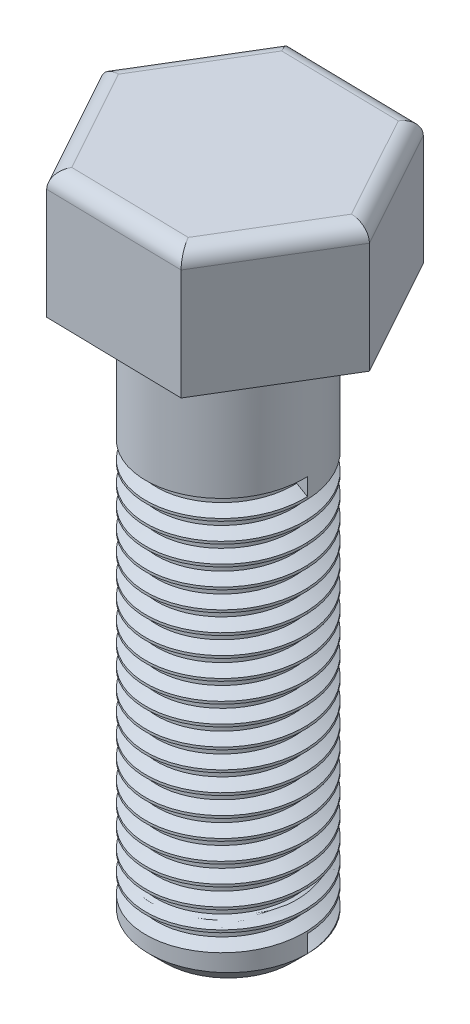
SolidWorks part; units mm, degrees
ref_plane "Front Plane" through (0, 0, 0) normal (0, 0, 1) x (1, 0, 0)
ref_plane "Top Plane" through (0, 0, 0) normal (0, 1, 0) x (1, 0, 0)
ref_plane "Right Plane" through (0, 0, 0) normal (1, 0, 0) x (0, 0, -1)
sketch "Sketch1" plane through (0, 0, 0) normal (0, 1, 0) x (1, 0, 0)
  circle A0 centre (0, 0) radius 5
  dimension "D1" = 10
extrude "Boss-Extrude1" add sketch "Sketch1" along normal blind 35
sketch "Sketch4" plane through (0, 35, 0) normal (0, 1, 0) x (1, 0, 0)
  line L1 (4.9182, 7.3997) -> (-3.7404, 7.5714)
  line L2 (-3.7404, 7.5714) -> (-8.2184, 0.1587)
  line L3 (-8.2184, 0.1587) -> (-4.0378, -7.4256)
  line L4 (-4.0378, -7.4256) -> (4.6208, -7.5973)
  line L5 (4.6208, -7.5973) -> (9.0987, -0.1847)
  line L6 (9.0987, -0.1847) -> (4.9182, 7.3997)
  circle A0 centre (0.4402, -0.013) radius 7.5 construction
  dimension "D1" = 15
extrude "Boss-Extrude2" add sketch "Sketch4" along normal blind 8
fillet "Fillet1" radius 1 6 edges at (6.8598, 43, 3.891) (0.2915, 43, 7.5115) (-6.1281, 43, 3.6335) (-5.9794, 43, -3.8651) (0.5889, 43, -7.4856) (7.0084, 43, -3.6075)
fillet "Fillet3" radius 1 1 edges at (0, 35, 5)
chamfer "Chamfer1" distance 1 angle 45 1 edges at (0, 0, 5)
thread "Thread2" pitch 1.25 method cut profile "Thread Profile2" start angle 0, offset 0, length 25, pitch 1.25, diameter 10
ref_plane "Plane2" through (5, 1, 0) normal (0, 0, 1) x (1, 0, 0)
sketch "Thread Profile2" plane through (5, 1, 0) normal (0, 0, 1) x (1, 0, 0)
  line L0 (0, 0) -> (0, 1.25) construction
  line L11 (0, 0) -> (0, 1.0937)
  line L12 (0, 1.0937) -> (-0.6766, 0.7031)
  line L13 (-0.6766, 0.7031) -> (-0.6766, 0.3906)
  line L15 (-0.6766, 0.3906) -> (0, 0)
  line L17 (-0.6766, 0.5469) -> (0, 0.5469) construction
  point P2 (0, 0)
  dimension "Pitch" = 1.25
  dimension "Profile_Angle" = 60
  dimension "Profile_Land" = 0.3125
  dimension "Profile_Height" = 0.6766
